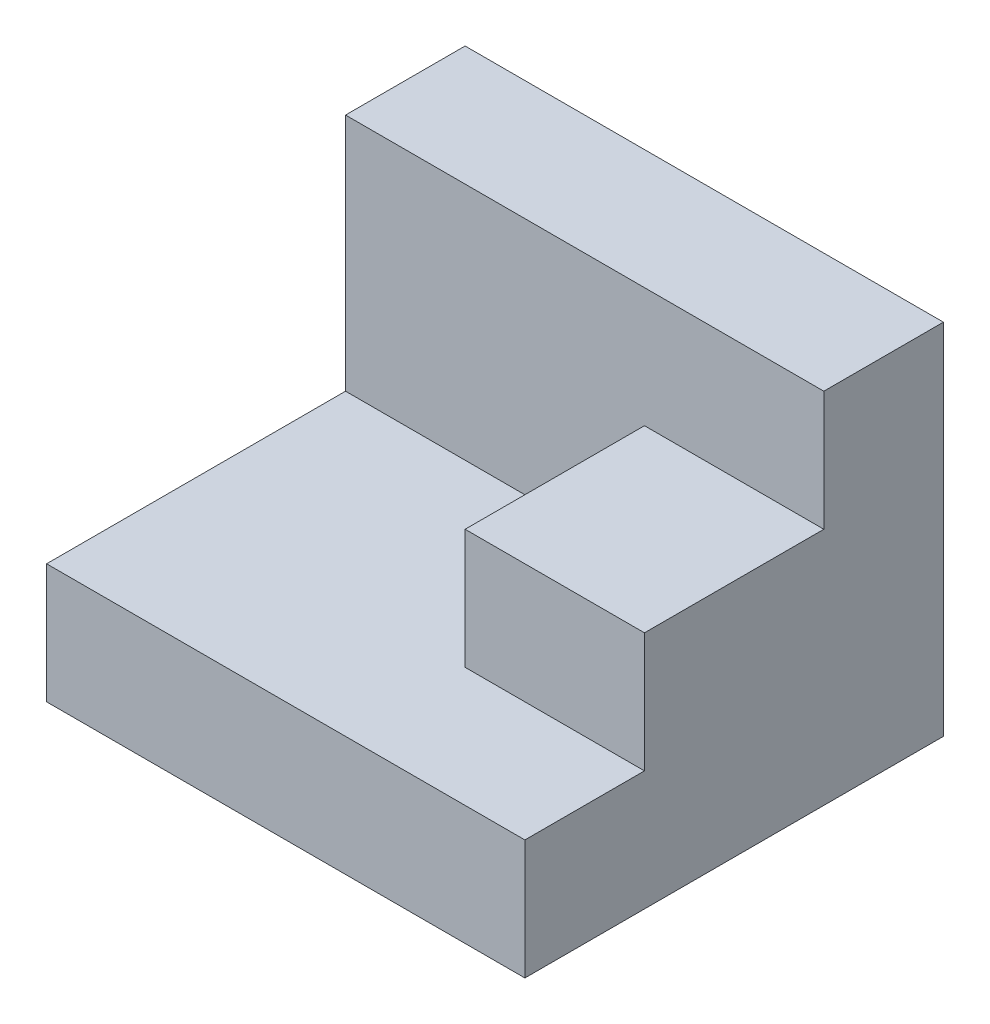
SolidWorks part; units mm, degrees
ref_plane "Front Plane" through (0, 0, 0) normal (0, 0, 1) x (1, 0, 0)
ref_plane "Top Plane" through (0, 0, 0) normal (0, 1, 0) x (1, 0, 0)
ref_plane "Right Plane" through (0, 0, 0) normal (1, 0, 0) x (0, 0, -1)
sketch "Sketch2" plane through (0, 0, 0) normal (0, 0, 1) x (1, 0, 0)
  line L0 (0, 0) -> (40, 0)
  line L1 (40, 0) -> (40, 10)
  line L2 (40, 10) -> (0, 10)
  line L3 (0, 10) -> (0, 0)
  line L4 (0, 10) -> (0, 30)
  line L5 (0, 30) -> (40, 30)
  line L6 (40, 30) -> (40, 10)
  line L7 (25, 10) -> (25, 20)
  line L8 (25, 20) -> (40, 20)
  dimension "D1" = 40
  dimension "D2" = 10
  dimension "D3" = 20
  dimension "D4" = 15
extrude "Boss-Extrude1" add sketch "Sketch2" along normal blind 25 contours L2 L3 L0 L1 region at (20, 5, 0)
extrude "Boss-Extrude2" add sketch "Sketch2<5>" along normal blind 15 contours L8 L7 L2 L6 region at (32.5, 15, 0)
sketch "Sketch2<5>" plane through (0, 0, 0) normal (0, 0, 1) x (1, 0, 0) same geometry as "Sketch2"
extrude "Boss-Extrude3" add sketch "Sketch2<7>" against normal blind 10 contours L7 L8 L6 L5 L4 L2 | L8 L7 L2 L6 | L2 L3 L0 L1 region at (20, 5, 0) region at (17.1154, 21.1538, 0) region at (32.5, 15, 0)
sketch "Sketch2<7>" plane through (0, 0, 0) normal (0, 0, 1) x (1, 0, 0) same geometry as "Sketch2"
